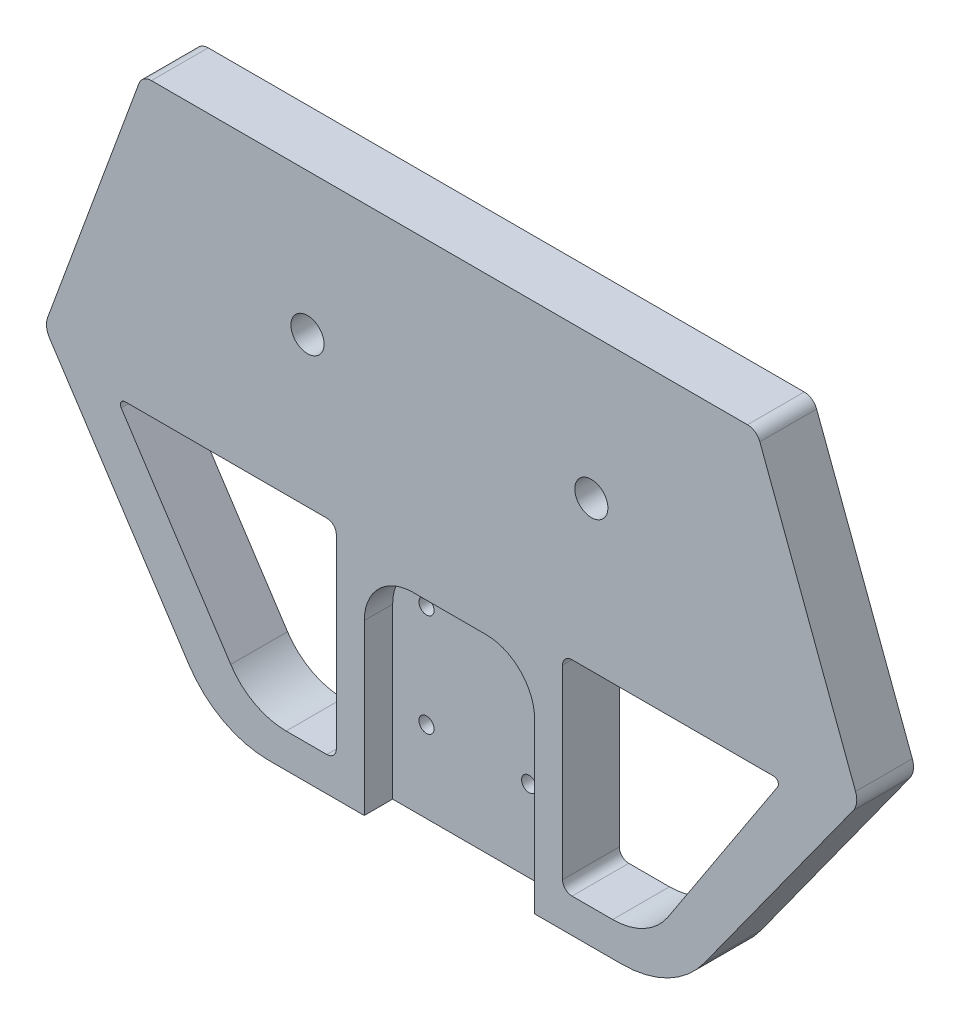
SolidWorks part; units mm, degrees
ref_plane "Front Plane" through (0, 0, 0) normal (0, 0, 1) x (1, 0, 0)
ref_plane "Top Plane" through (0, 0, 0) normal (0, 1, 0) x (1, 0, 0)
ref_plane "Right Plane" through (0, 0, 0) normal (1, 0, 0) x (0, 0, -1)
sketch "Sketch2" plane through (0, 0, 0) normal (0, 0, 1) x (1, 0, 0)
  line L0 (0, 84.074) -> (0, -72.39) construction
  line L1 (40.005, 34.1945) -> (-40.005, 34.1945)
  line L3 (-53.9331, -0.3154) -> (-41.6738, 33.03)
  line L4 (54.516, -1.1878) -> (41.6696, 33.0412)
  line L5 (-53.6746, -2.5826) -> (-34.9601, -31.1835)
  line L6 (-24.2904, -36.9528) -> (23.1203, -36.9528)
  line L7 (34.2093, -31.2786) -> (54.198, -3.5662)
  arc A1 (-40.005, 34.1945) -> (-41.6738, 33.03) centre (-40.005, 32.4165) ccw
  arc A3 (40.005, 34.1945) -> (41.6696, 33.0412) centre (40.005, 32.4165) cw
  circle A4 centre (-19.05, 15.1445) radius 2.2225
  circle A5 centre (19.05, 15.1445) radius 2.2225
  arc A6 (-24.2904, -36.9528) -> (-34.9601, -31.1835) centre (-24.2904, -24.202) cw
  arc A7 (23.1203, -36.9528) -> (34.2093, -31.2786) centre (23.1203, -23.2803) ccw
  arc A8 (-53.6746, -2.5826) -> (-53.9331, -0.3154) centre (-51.5491, -1.1919) cw
  arc A9 (54.516, -1.1878) -> (54.198, -3.5662) centre (52.1379, -2.0803) cw
  point P4 (0, 57.6776)
  point P9 (0, 19.5776)
  point P19 (-31.1851, -36.9528)
  point P20 (0, -3.9055)
  point P25 (30.1165, -36.9528)
  point P28 (-54.3738, -1.514)
  point P31 (54.9942, -2.4622)
  dimension "D2" = 23.1203
  dimension "D3" = 24.2904
  dimension "D6" = 4.445
  dimension "D4" = 36.9528
  dimension "D5" = 12.7508
  dimension "D7" = 2.54
  dimension "D8" = 2.54
  dimension "D9" = 1.778
  dimension "D10" = 19.05
  dimension "D11" = 15.1445
  dimension "D12" = 13.6725
  dimension "D1" = 36.8046
extrude "Boss-Extrude1" add sketch "Sketch2" along normal blind 7.62
sketch "Sketch3" plane through (0, 0, 7.62) normal (0, 0, 1) x (1, 0, 0)
  line L0 (0, 22.8554) -> (0, -43.592) construction
  line L7 (-24.2904, -36.9528) -> (23.1203, -36.9528) construction
  circle A0 centre (-6.887, -26.0308) radius 1.016
  circle A1 centre (-6.887, -12.2569) radius 1.016
  circle A6 centre (6.887, -12.2569) radius 1.016
  circle A7 centre (6.887, -26.0308) radius 1.016
  dimension "D4" = 10.922
  dimension "D1" = 6.887
  dimension "D2" = 13.7739
  dimension "D3" = 2.032
extrude "Cut-Extrude1" cut sketch "Sketch3" against normal through all both and the other way through all
sketch "Sketch4" plane through (0, 0, 7.62) normal (0, 0, 1) x (1, 0, 0)
  line L0 (0, 3.0374) -> (0, -49.2989) construction
  line L1 (4.8847, -7.7421) -> (-4.8847, -7.7421)
  line L2 (-11.43, -14.2874) -> (-11.43, -37.5871)
  line L3 (-11.43, -37.5871) -> (11.43, -37.5871)
  line L4 (-24.2904, -36.9528) -> (23.1203, -36.9528) construction
  line L5 (11.43, -14.2874) -> (11.43, -37.5871)
  arc A0 (-4.8847, -7.7421) -> (-11.43, -14.2874) centre (-4.8847, -14.2874) ccw
  arc A1 (4.8847, -7.7421) -> (11.43, -14.2874) centre (4.8847, -14.2874) cw
  point P9 (-11.43, -7.7421)
  point P14 (0, -7.7421)
  point P17 (0, -37.5871)
  dimension "D1" = 11.43
  dimension "D3" = 29.845
  dimension "D4" = 0.6343
extrude "Cut-Extrude2" cut sketch "Sketch4" against normal blind 3.81 and the other way through all
sketch "Sketch5" plane through (0, 0, 0) normal (0, 0, -1) x (-1, 0, 0)
  line L0 (0, -24.2327) -> (0, 20.0285) construction
  circle A0 centre (-6.887, -12.2569) radius 1.905
  circle A1 centre (-6.887, -26.0308) radius 1.905
  circle A2 centre (6.887, -26.0308) radius 1.905
  circle A3 centre (6.887, -12.2569) radius 1.905
  dimension "D1" = 3.81
  dimension "D2" = 3.81
extrude "Cut-Extrude3" cut sketch "Sketch5" against normal blind 0.635
sketch "Sketch6" plane through (0, 0, 7.62) normal (0, 0, 1) x (1, 0, 0)
  line L0 (0, -25.1696) -> (0, 28.2164) construction
  line L3 (-44.0566, -5.8812) -> (-29.3539, -28.3511)
  line L4 (-53.6746, -2.5826) -> (-34.9601, -31.1835) construction
  line L5 (-54.0728, -1.4797) -> (0, -1.4797) construction
  line L6 (-43.5253, -4.8985) -> (-16.453, -4.8985)
  line L7 (-15.183, -6.1685) -> (-15.183, -31.1035)
  line L8 (-16.453, -32.3735) -> (-21.9149, -32.3735)
  line L9 (16.453, -32.3735) -> (21.9149, -32.3735)
  line L10 (15.183, -6.1685) -> (15.183, -31.1035)
  line L11 (43.5253, -4.8985) -> (16.453, -4.8985)
  line L12 (44.0566, -5.8812) -> (29.3539, -28.3511)
  line L15 (-11.43, -14.2874) -> (-11.43, -36.9528) construction
  line L16 (11.43, -36.9528) -> (23.1203, -36.9528) construction
  arc A3 (-53.9331, -0.3154) -> (-53.6746, -2.5826) centre (-51.5491, -1.1919) ccw construction
  arc A4 (-21.9149, -32.3735) -> (-29.3539, -28.3511) centre (-21.9149, -23.4835) cw
  arc A5 (-15.183, -31.1035) -> (-16.453, -32.3735) centre (-16.453, -31.1035) cw
  arc A6 (-15.183, -6.1685) -> (-16.453, -4.8985) centre (-16.453, -6.1685) ccw
  arc A7 (-43.5253, -4.8985) -> (-44.0566, -5.8812) centre (-43.5253, -5.5335) ccw
  arc A8 (43.5253, -4.8985) -> (44.0566, -5.8812) centre (43.5253, -5.5335) cw
  arc A9 (15.183, -6.1685) -> (16.453, -4.8985) centre (16.453, -6.1685) cw
  arc A10 (15.183, -31.1035) -> (16.453, -32.3735) centre (16.453, -31.1035) ccw
  arc A11 (21.9149, -32.3735) -> (29.3539, -28.3511) centre (21.9149, -23.4835) ccw
  dimension "D1" = 8.89
  dimension "D2" = 34.5503
  dimension "D3" = 3.753
  dimension "D4" = 0.635
  dimension "D8" = 1.27
  dimension "D5" = 10.4849
  dimension "D6" = 32.0953
  dimension "D7" = 4.5793
  dimension "D9" = 22.6654
extrude "Cut-Extrude4" cut sketch "Sketch6" against normal through all
